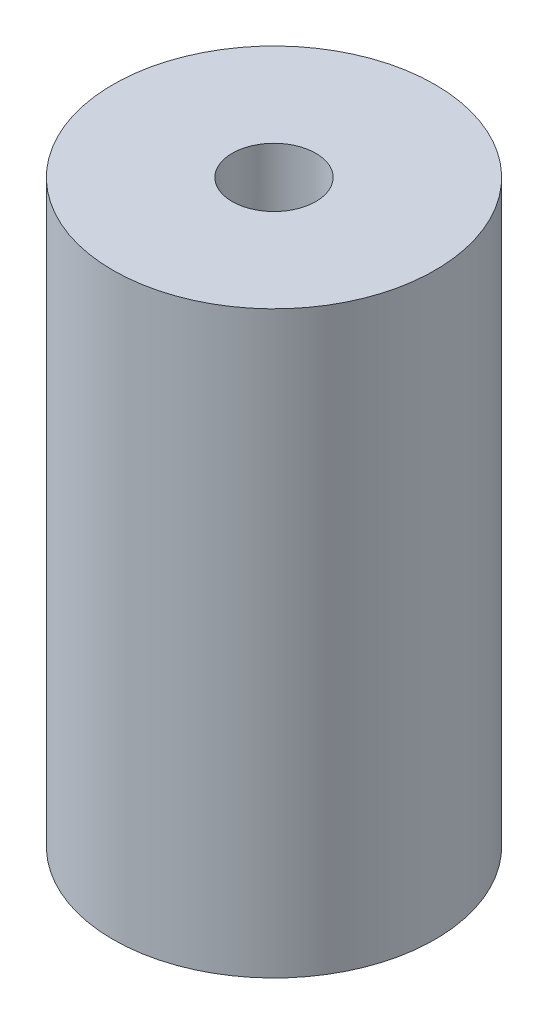
SolidWorks part; units mm, degrees
material "AISI 1020"
ref_plane "Front Plane" through (0, 0, 0) normal (0, 0, 1) x (1, 0, 0)
ref_plane "Top Plane" through (0, 0, 0) normal (0, 1, 0) x (1, 0, 0)
ref_plane "Right Plane" through (0, 0, 0) normal (1, 0, 0) x (0, 0, -1)
sketch "Sketch1" plane through (0, 0, 0) normal (0, 1, 0) x (1, 0, 0)
  circle A0 centre (0, 0) radius 250
extrude "Boss-Extrude1" add sketch "Sketch1" along normal blind 900 contours A0
sketch "Sketch5" plane through (0, 0, 0) normal (0, -1, 0) x (-1, 0, 0)
  circle A0 centre (0, 0) radius 200
  dimension "D1" = 400
extrude "Cut-Extrude1" cut sketch "Sketch5" against normal blind 700 from offset 100 contours A0 offset against normal yes
sketch "Sketch6" plane through (0, 900, 0) normal (0, 1, 0) x (1, 0, 0)
  circle A0 centre (0, 0) radius 65
  dimension "D1" = 130
extrude "Cut-Extrude2" cut sketch "Sketch6" against normal blind 1356
